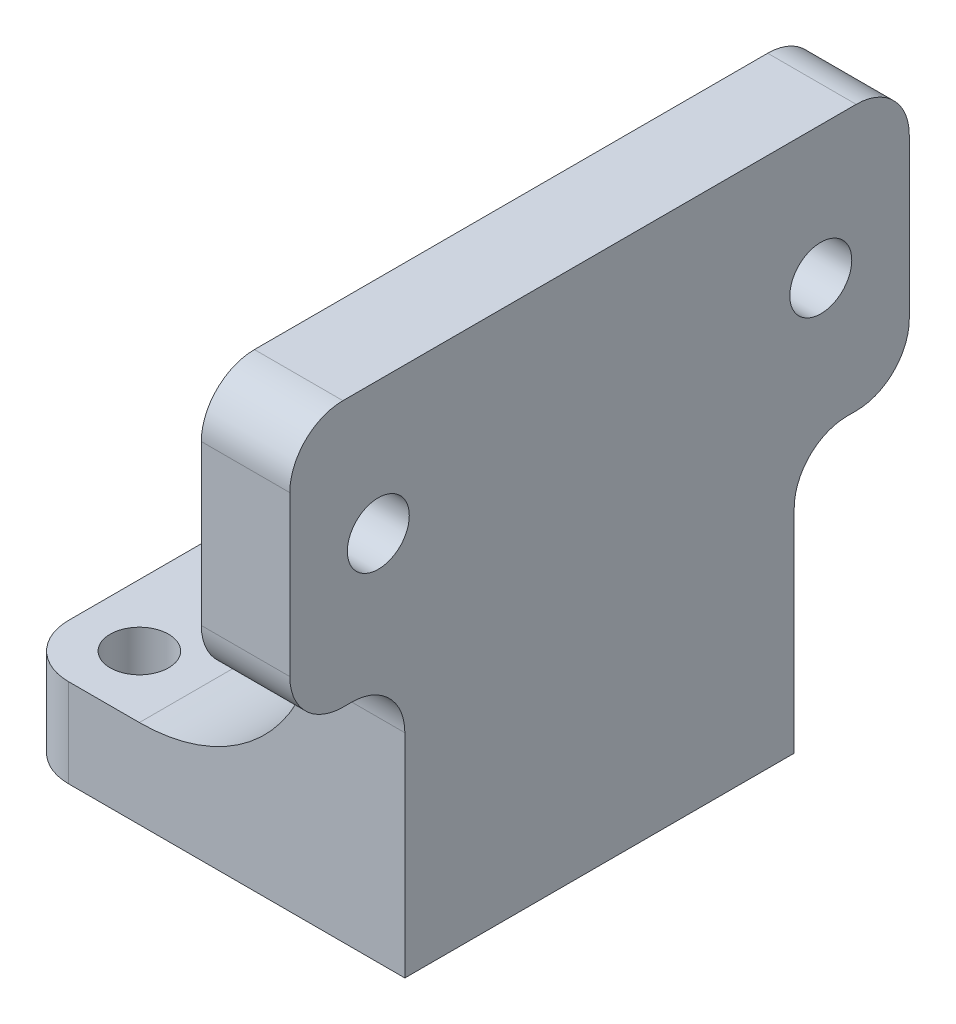
SolidWorks part; units mm, degrees
material "ABS"
ref_plane "Front Plane" through (0, 0, 0) normal (0, 0, 1) x (1, 0, 0)
ref_plane "Top Plane" through (0, 0, 0) normal (0, 1, 0) x (1, 0, 0)
ref_plane "Right Plane" through (0, 0, 0) normal (1, 0, 0) x (0, 0, -1)
sketch "Sketch1" plane through (0, 0, 0) normal (0, 1, 0) x (1, 0, 0)
  line L0 (0, 11) -> (22, 11) construction
  line L1 (0, 0) -> (22, 0)
  line L2 (0, 0) -> (0, 22)
  line L3 (0, 22) -> (22, 22)
  line L4 (22, 0) -> (22, 22)
  line L5 (17, 22) -> (17, 0) construction
  line L6 (3.5, 22) -> (3.5, 0) construction
  circle A1 centre (13.5, 11) radius 1.65
  circle A3 centre (3.5, 3.5) radius 1.65
  circle A6 centre (3.5, 18.5) radius 1.65
  point P17 (0, 0)
  point P18 (13.5, 11)
  point P19 (3.5, 18.5)
  dimension "D5" = 3.3
  dimension "D1" = 22
  dimension "D2" = 5
  dimension "D3" = 3.5
  dimension "D4" = 3.5
  dimension "D7" = 3.5
  dimension "D8" = 22
extrude "Boss-Extrude1" add sketch "Sketch1" along normal blind 5
sketch "Sketch2" plane through (0, 5, 0) normal (0, 1, 0) x (1, 0, 0)
  line L0 (0, 0) -> (22, 0) construction
  line L1 (22, 22) -> (17, 22)
  line L2 (22, 22) -> (22, 0)
  line L3 (22, 0) -> (17, 0)
  line L4 (17, 22) -> (17, 0)
  dimension "D1" = 5
extrude "Boss-Extrude2" add sketch "Sketch2" along normal blind 10
sketch "Sketch3" plane through (17, 0, 0) normal (-1, 0, 0) x (0, 0, 1)
  line L0 (-11, 15) -> (-11, 5) construction
  line L1 (-22, 15) -> (0, 15) construction
  line L2 (-22, 5) -> (0, 5) construction
  line L4 (-14.5, 15) -> (-7.5, 15)
  line L5 (-14.5, 15) -> (-14.5, 5)
  line L6 (-14.5, 5) -> (-7.5, 5)
  line L7 (-7.5, 15) -> (-7.5, 5)
  dimension "D1" = 7
extrude "Cut-Extrude1" cut sketch "Sketch3" against normal blind 0.1
fillet "Fillet1" radius 10 2 edges at (17, 5, -18.25) (17, 5, -3.75)
sketch "Sketch5" plane through (22, 0, 0) normal (1, 0, 0) x (0, 0, -1)
  line L0 (11, 30) -> (11, 0) construction
  line L1 (-6.5, 15) -> (28.5, 15)
  line L2 (-6.5, 15) -> (-6.5, 30)
  line L3 (-6.5, 30) -> (28.5, 30)
  line L4 (28.5, 15) -> (28.5, 30)
  line L5 (0, 0) -> (22, 0) construction
  line L6 (-6.5, 22.5) -> (28.5, 22.5) construction
  line L7 (0, 15) -> (22, 15) construction
  circle A0 centre (23.5, 22.5) radius 1.75
  circle A1 centre (-1.5, 22.5) radius 1.75
  point P16 (11, 15)
  dimension "D5" = 3.5
  dimension "D1" = 5
  dimension "D2" = 5
  dimension "D3" = 25
  dimension "D4" = 15
extrude "CHANGE THIS SKETCH" add sketch "Sketch5" against normal blind 5
fillet "Fillet2" radius 3 8 edges at (19.5, 15, -22) (19.5, 15, 0) (19.5, 30, -28.5) (19.5, 15, -28.5) (0, 2.5, -22) (0, 2.5, 0) (19.5, 30, 6.5) (19.5, 15, 6.5)
